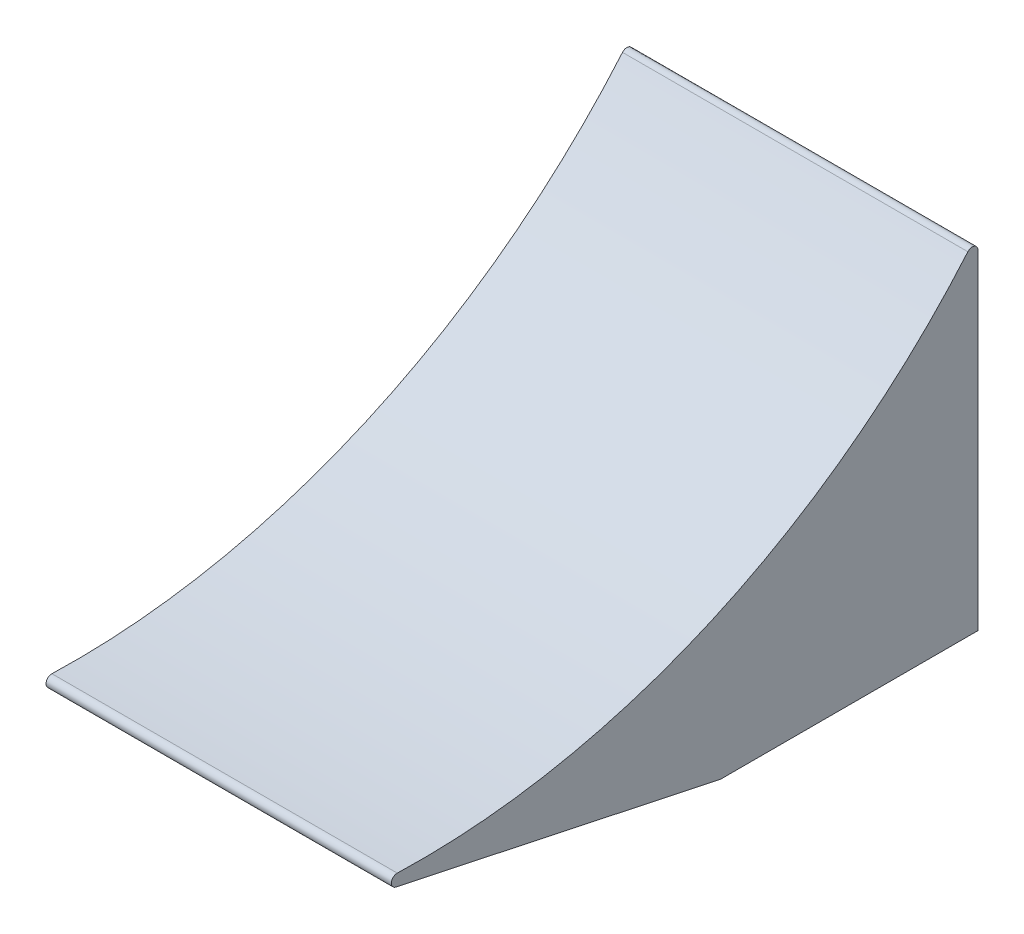
SolidWorks part; units mm, degrees
ref_plane "Front" through (0, 0, 0) normal (0, 0, 1) x (1, 0, 0)
ref_plane "Top" through (0, 0, 0) normal (0, 1, 0) x (1, 0, 0)
ref_plane "Right" through (0, 0, 0) normal (1, 0, 0) x (0, 0, -1)
sketch "Sketch1" plane through (0, 0, 0) normal (1, 0, 0) x (0, 0, -1)
  line L0 (28.4228, 0) -> (-28.4228, 0)
  line L2 (28.4228, 76.2) -> (28.4228, 0)
  line L3 (-28.4228, 0) -> (-127.8026, 21.1238)
  line L6 (-182.8607, 32.8268) -> (-186.9601, 33.6981) construction
  arc A0 (-127.8026, 21.1238) -> (28.4228, 76.2) centre (-94.7696, 176.532) ccw
  point P4 (0, 0)
  point P7 (-46.4474, 3.8312)
  point P8 (-46.4474, 3.8312)
  point P9 (-89.4064, 12.9625)
  dimension "D3" = 101.6
  dimension "D1" = 76.2
extrude "Boss-Extrude1" add sketch "Sketch1" along normal mid plane 76.2 contours L2 L0 L3 A0
fillet "Fillet1" radius 1.27 2 edges at (0, 76.2, -28.4228) (0, 21.1238, 127.8026)
